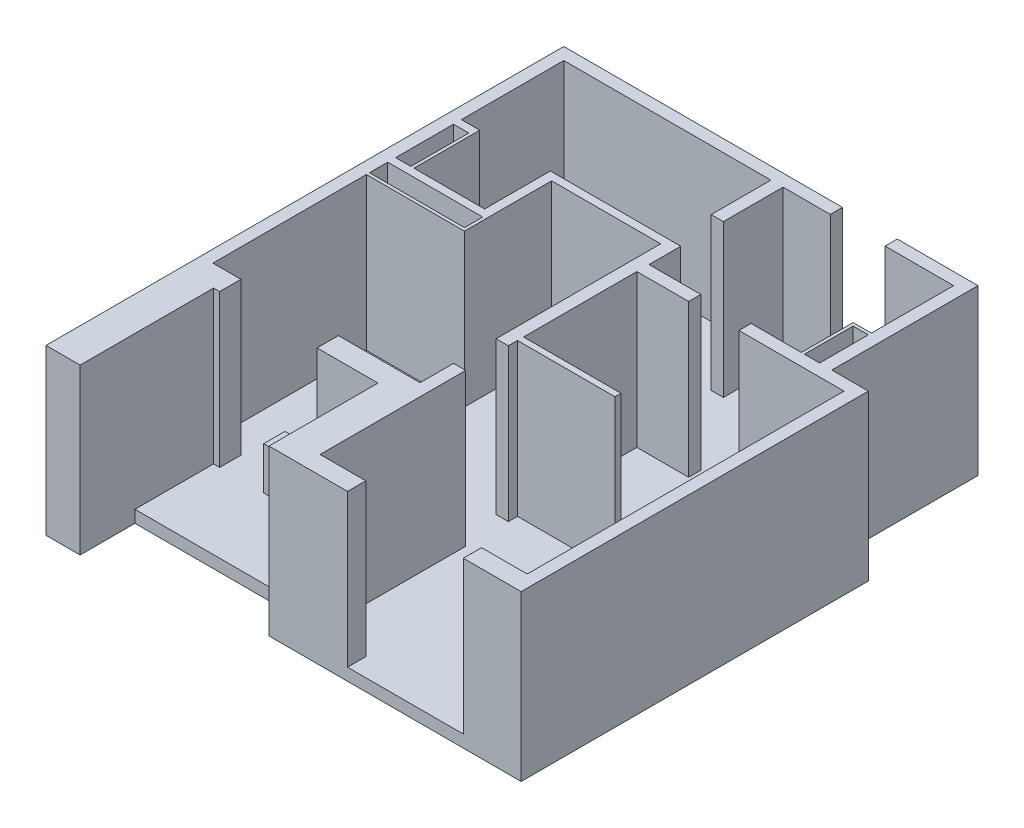
SolidWorks part; units mm, degrees
ref_plane "Спереди" through (0, 0, 0) normal (0, 0, 1) x (1, 0, 0)
ref_plane "Сверху" through (0, 0, 0) normal (0, 1, 0) x (1, 0, 0)
ref_plane "Справа" through (0, 0, 0) normal (1, 0, 0) x (0, 0, -1)
other "Configuration Table"
sketch "чертеж" plane through (0, 0, 0) normal (0, 1, 0) x (1, 0, 0)
  line L0 (-122.4645, -5934.5928) -> (200.8688, -5934.5928) construction
  line L1 (11.3792, -6202.3586) -> (334.7125, -6202.3586) construction
  line L2 (-29.7674, 42.6262) -> (294.8993, 42.6262) construction
  line L3 (-41.8231, 39.2884) -> (282.8435, 39.2884) construction
  line L4 (2418.4622, -1094.6493) -> (2743.1288, -1094.6493) construction
  line L5 (-60.4594, 42.9789) -> (264.2073, 42.9789) construction
  line L6 (-48.7728, 66.0913) -> (275.8939, 66.0913) construction
  line L7 (-42.5542, 93.9023) -> (282.1124, 93.9023) construction
  line L8 (134.2311, 87.3942) -> (458.8978, 87.3942) construction
  line L9 (-47.3906, 51.9395) -> (277.2761, 51.9395) construction
  line L10 (-66.0858, -48.647) -> (431.2475, -48.647) construction
sketch "Эскиз по чертежу" plane through (0, 0, 0) normal (0, 1, 0) x (1, 0, 0)
  line L0 (0, 0) -> (0, 8400) construction
  line L1 (0, 8400) -> (1925, 8400) construction
  line L2 (6600, 8400) -> (6600, 6000) construction
  line L4 (7200, 6000) -> (7200, 600) construction
  line L5 (7200, 600) -> (3600, 600) construction
  line L6 (3600, 600) -> (3600, 8400) construction
  line L7 (3600, 2400) -> (0, 2400) construction
  line L8 (3600, 5475) -> (0, 5475) construction
  line L32 (6600, 6000) -> (7200, 6000) construction
  line L33 (0, 900) -> (3600, 900) construction
  line L37 (0, 1050) -> (3600, 1050) construction
  line L40 (1925, 5475) -> (1925, 6550) construction
  line L42 (1925, 6550) -> (1925, 8400) construction
  line L45 (1925, 8400) -> (3600, 8400) construction
  line L46 (3600, 8400) -> (6600, 8400) construction
  line L49 (1925, 6550) -> (0, 6550) construction
  dimension "D1" = 600
  dimension "D2" = 1800
  dimension "D3" = 3600
  dimension "D4" = 1500
  dimension "D5" = 600
  dimension "D6" = 3600
  dimension "D7" = 3600
  dimension "D8" = 2400
  dimension "D9" = 2925
  dimension "D10" = 1925
  dimension "D11" = 1850
  dimension "D12" = 1350
sketch "Эскиз3" plane through (0, 0, 0) normal (0, 1, 0) x (1, 0, 0)
  line L0 (0, 0) -> (0, 8400) construction
  line L1 (7200, 6000) -> (7200, 600) construction
  line L3 (6600, 8400) -> (6600, 6000) construction
  line L11 (100, 8300) -> (3500, 8300)
  line L15 (3500, 8300) -> (3500, 7700)
  line L16 (3500, 7700) -> (3700, 7700)
  line L17 (3700, 7700) -> (3700, 8300)
  line L19 (0, 8400) -> (1925, 8400) construction
  line L20 (6500, 6100) -> (5850, 6100)
  line L21 (-100, 8500) -> (4475, 8500)
  line L22 (6500, 8300) -> (6500, 6100)
  line L24 (4475, 8500) -> (4475, 8300)
  line L25 (4475, 8300) -> (3700, 8300)
  line L26 (6700, 8500) -> (5375, 8500)
  line L29 (7100, 5900) -> (7100, 700)
  line L30 (4450, 700) -> (3700, 700)
  line L32 (6350, 500) -> (7300, 500)
  line L33 (7300, 500) -> (7300, 6100)
  line L34 (7300, 6100) -> (6700, 6100)
  line L35 (6700, 6100) -> (6700, 8500)
  line L39 (5375, 8500) -> (5375, 8300)
  line L40 (5375, 8300) -> (6500, 8300)
  line L41 (5850, 6100) -> (5850, 5900)
  line L42 (5850, 5900) -> (7100, 5900)
  line L45 (-100, 8500) -> (-100, 0)
  line L46 (-100, 0) -> (100, 0)
  line L47 (3500, 6100) -> (4550, 6100)
  line L52 (100, 0) -> (100, 8300)
  line L60 (3700, 700) -> (3700, 5900)
  line L68 (3500, 6100) -> (3500, 500)
  line L69 (4550, 6100) -> (4550, 5900)
  line L70 (4550, 5900) -> (3700, 5900)
  line L71 (7100, 700) -> (6350, 700)
  line L72 (6350, 500) -> (6350, 700)
  line L73 (3500, 500) -> (4450, 500)
  line L74 (4450, 500) -> (4450, 700)
  line L75 (7200, 600) -> (3600, 600) construction
  dimension "D1" = 3400
  dimension "D2" = 3400
  dimension "D3" = 5200
  dimension "D4" = 1300
  dimension "D5" = 200
  dimension "D6" = 2800
  dimension "D7" = 200
  dimension "D8" = 200
  dimension "D9" = 2200
  dimension "D10" = 100
  dimension "D11" = 100
  dimension "D12" = 100
  dimension "D13" = 200
  dimension "D14" = 100
  dimension "D15" = 900
  dimension "D16" = 100
  dimension "D17" = 1125
  dimension "D18" = 600
  dimension "D19" = 200
  dimension "D20" = 850
  dimension "D21" = 1900
  dimension "D22" = 750
extrude "несущие стены" add sketch "Эскиз3" along normal blind 2500 separate body
sketch "Эскиз5" plane through (0, 0, 0) normal (0, 1, 0) x (1, 0, 0)
  line L0 (100, 6620) -> (1850, 6620)
  line L2 (1850, 6620) -> (1850, 7000)
  line L3 (1850, 7000) -> (2000, 7000)
  line L4 (2000, 7000) -> (2000, 6240)
  line L5 (2000, 6240) -> (1850, 6240)
  line L6 (1850, 6240) -> (1850, 6490)
  line L7 (1850, 6490) -> (100, 6490)
  line L9 (100, 6490) -> (100, 6620)
  line L10 (100, 5410) -> (2380, 5410)
  line L12 (2380, 5410) -> (2380, 5540)
  line L17 (2380, 5540) -> (100, 5540)
  line L18 (100, 5540) -> (100, 5410)
  line L19 (3500, 5410) -> (3280, 5410)
  line L20 (3500, 6100) -> (3500, 500) construction
  line L21 (3280, 5410) -> (3280, 5540)
  line L22 (3280, 5540) -> (3500, 5540)
  line L23 (100, 0) -> (100, 8300) construction
  line L24 (3500, 5540) -> (3500, 5410)
  line L25 (1850, 8300) -> (1850, 7700)
  line L27 (1850, 7700) -> (2000, 7700)
  line L28 (2000, 7700) -> (2000, 8300)
  line L30 (2000, 8300) -> (1850, 8300)
  line L31 (100, 8300) -> (3500, 8300) construction
  line L32 (3500, 8300) -> (3500, 7700) construction
  point P34 (3280, 5475)
  dimension "D1" = 600
  dimension "D2" = 1750
  dimension "D3" = 1500
  dimension "D4" = 1680
  dimension "D5" = 130
  dimension "D6" = 700
  dimension "D7" = 700
  dimension "D8" = 950
  dimension "D9" = 900
  dimension "D10" = 220
  dimension "D11" = 150
  dimension "D12" = 130
extrude "перегородки санузла" add sketch "Эскиз5" along normal up to surface (2500 mm away) up to face at (6453.5714, 2500, -5157.1429)
sketch "Эскиз7" plane through (0, 0, 0) normal (0, 1, 0) x (1, 0, 0)
  line L0 (100, 0) -> (100, 5410) construction
  line L1 (560, 2540) -> (100, 2540)
  line L2 (460, 2190) -> (460, 0)
  line L3 (3160, 2190) -> (3160, 400)
  line L4 (3160, 400) -> (4450, 400)
  line L5 (460, 0) -> (100, 0)
  line L6 (100, 2540) -> (100, 0)
  line L7 (3280, 5410) -> (3500, 5410) construction
  line L8 (3160, 2190) -> (2160, 2190)
  line L9 (3500, 500) -> (4450, 500) construction
  line L10 (2160, 2540) -> (3500, 2540)
  line L19 (4450, 500) -> (4450, 400)
  line L20 (6350, 500) -> (7300, 500)
  line L21 (6350, 500) -> (6350, 400)
  line L22 (6350, 400) -> (7300, 400)
  line L23 (7300, 500) -> (7300, 400)
  line L24 (2160, 2190) -> (2160, 2540)
  line L25 (3500, 2540) -> (3500, 500)
  line L26 (3500, 500) -> (4450, 500)
  line L27 (3500, 5410) -> (3500, 500) construction
  line L28 (6350, 500) -> (7300, 500) construction
  line L29 (460, 2190) -> (560, 2190)
  line L30 (560, 2190) -> (560, 2540)
  line L31 (4450, 500) -> (4450, 700) construction
  line L32 (6350, 700) -> (6350, 500) construction
  dimension "D1" = 2700
  dimension "D2" = 100
  dimension "D3" = 350
  dimension "D4" = 1600
  dimension "D5" = 100
  dimension "D6" = 460
  dimension "D7" = 2870
extrude "лоджия" add sketch "Эскиз7" along normal up to surface (2500 mm away) up to face at (6453.5714, 2500, -5157.1429)
sketch "Эскиз8" plane through (0, 0, 0) normal (0, 1, 0) x (1, 0, 0)
  line L1 (50, 5460) -> (1710, 5460)
  line L2 (50, 5460) -> (50, 5060)
  line L3 (50, 5060) -> (1710, 5060)
  line L4 (1710, 5460) -> (1710, 5060)
  line L5 (100, 5410) -> (1660, 5410)
  line L6 (100, 5410) -> (100, 5110)
  line L7 (100, 5110) -> (1660, 5110)
  line L8 (1660, 5410) -> (1660, 5110)
  line L9 (100, 5410) -> (2380, 5410) construction
  line L10 (100, 2540) -> (100, 5410) construction
  dimension "D1" = 350
  dimension "D2" = 50
  dimension "D3" = 50
  dimension "D4" = 50
  dimension "D5" = 1610
  dimension "D6" = 50
extrude "вытяжка кухня" add sketch "Эскиз8" along normal up to surface (2500 mm away) up to face at (6453.5714, 2500, -5142.8571)
sketch "Эскиз9" plane through (0, 0, 0) normal (0, 1, 0) x (1, 0, 0)
  line L1 (6550, 6950) -> (6200, 6950)
  line L2 (6550, 6950) -> (6550, 6050)
  line L3 (6550, 6050) -> (6200, 6050)
  line L4 (6200, 6950) -> (6200, 6050)
  line L6 (6500, 6100) -> (5850, 6100) construction
  line L7 (6250, 6900) -> (6500, 6900)
  line L8 (6250, 6900) -> (6250, 6100)
  line L9 (6250, 6100) -> (6500, 6100)
  line L10 (6500, 6900) -> (6500, 6100)
  line L11 (6500, 8300) -> (6500, 6100) construction
  line L12 (50, 6540) -> (400, 6540)
  line L14 (400, 6540) -> (400, 5490)
  line L16 (400, 5490) -> (50, 5490)
  line L17 (50, 5490) -> (50, 6540)
  line L18 (100, 6490) -> (350, 6490)
  line L19 (350, 6490) -> (350, 5540)
  line L20 (350, 5540) -> (100, 5540)
  line L21 (100, 5540) -> (100, 6490)
  line L22 (1850, 6490) -> (1850, 6240) construction
  line L23 (100, 6490) -> (1850, 6490) construction
  point P13 (6375, 6950)
  dimension "D1" = 850
  dimension "D2" = 50
  dimension "D3" = 50
  dimension "D4" = 300
  dimension "D5" = 50
  dimension "D6" = 50
  dimension "D7" = 50
  dimension "D8" = 50
  dimension "D9" = 50
  dimension "D10" = 50
  dimension "D11" = 1450
extrude "зсс" add sketch "Эскиз9" along normal up to surface (2500 mm away) up to face at (6453.5714, 2500, -5142.8571)
sketch "Эскиз11" plane through (0, 0, 0) normal (0, 1, 0) x (1, 0, 0)
  line L1 (2160, 2540) -> (1284, 2540)
  line L2 (2160, 2540) -> (2160, 2190)
  line L3 (2160, 2190) -> (1284, 2190)
  line L4 (1284, 2540) -> (1284, 2190)
  line L5 (560, 2190) -> (560, 2540) construction
  dimension "D1" = 724
extrude "лоджияперегородка" add sketch "Эскиз11" along normal blind 700
sketch "Эскиз4" plane through (0, 0, 0) normal (0, 1, 0) x (1, 0, 0)
  line L8 (-100, 8500) -> (6700, 8500)
  line L9 (6700, 8500) -> (6700, 6100)
  line L10 (6700, 6100) -> (7300, 6100)
  line L11 (7300, 6100) -> (7300, 400)
  line L13 (3160, 400) -> (3160, 900)
  line L14 (3160, 900) -> (460, 900)
  line L17 (-100, 0) -> (-100, 8500)
  line L18 (6700, 6100) -> (6700, 8500) construction
  line L19 (6700, 8500) -> (5375, 8500) construction
  line L23 (0, 900) -> (3600, 900) construction
  line L24 (460, 900) -> (460, 0)
  line L25 (460, 0) -> (-100, 0)
  line L26 (3160, 400) -> (7300, 400)
  line L27 (3160, 2190) -> (3160, 400) construction
  line L28 (460, 0) -> (460, 2190) construction
  line L29 (-100, 0) -> (460, 0) construction
extrude "пол" add sketch "Эскиз4" against normal blind 200
sketch "Эскиз что надо" [suppressed] plane through (0, 0, 0) normal (0, 1, 0) x (1, 0, 0)
  line L0 (5525, 8300) -> (5525, 6100) construction
  line L5 (2000, 6240) -> (2000, 7000) construction
  line L6 (1850, 7000) -> (2000, 7000)
  line L7 (1850, 7000) -> (1850, 6620)
  line L8 (1850, 6620) -> (2000, 6620)
  line L9 (2000, 7000) -> (2000, 6620)
  line L10 (1850, 6490) -> (1850, 6240) construction
  line L11 (1850, 7700) -> (2000, 7700)
  line L12 (1850, 7700) -> (1850, 7320)
  line L13 (1850, 7320) -> (2000, 7320)
  line L14 (2000, 7700) -> (2000, 7320)
  line L15 (1850, 5540) -> (2000, 5540)
  line L16 (1850, 5540) -> (1850, 5790)
  line L17 (1850, 5790) -> (2000, 5790)
  line L18 (2000, 5540) -> (2000, 5790)
  line L19 (1850, 6490) -> (2000, 6490)
  line L20 (1850, 6490) -> (1850, 6240)
  line L21 (1850, 6240) -> (2000, 6240)
  line L22 (2000, 6490) -> (2000, 6240)
  line L23 (1850, 7000) -> (1850, 6620) construction
  line L28 (3500, 7700) -> (3700, 7700) construction
  line L29 (3500, 7700) -> (3500, 7420) construction
  line L30 (3500, 7420) -> (3700, 7420) construction
  line L31 (3700, 7700) -> (3700, 7420) construction
  line L32 (4550, 5900) -> (4550, 6100) construction
  line L35 (5850, 5900) -> (5450, 5900)
  line L36 (5850, 5900) -> (5850, 6100)
  line L37 (5850, 6100) -> (5450, 6100)
  line L38 (5450, 5900) -> (5450, 6100)
  line L39 (5375, 8300) -> (6500, 8300) construction
  line L40 (2000, 7420) -> (3500, 7420) construction
  line L41 (5375, 8500) -> (5375, 8300) construction
  line L42 (2380, 5540) -> (400, 5540) construction
  line L43 (1284, 2540) -> (2160, 2540)
  line L44 (1284, 2540) -> (1284, 2190)
  line L46 (1284, 2190) -> (2160, 2190)
  line L47 (2000, 7320) -> (2000, 6620) construction
  line L48 (2160, 2540) -> (2160, 2190)
  point P32 (1925, 6490)
  dimension "D8" = 900
  dimension "D1" = 700
  dimension "D2" = 700
  dimension "D3" = 150
  dimension "D5" = 100
sketch "Эскиз13" [suppressed] plane through (0, 0, 0) normal (0, 1, 0) x (1, 0, 0)
  line L1 (1850, 6490) -> (2000, 6490)
  line L2 (1850, 6490) -> (1850, 6240)
  line L3 (1850, 6240) -> (2000, 6240)
  line L4 (2000, 6490) -> (2000, 6240)
  line L5 (1850, 7000) -> (2000, 7000)
  line L6 (1850, 7000) -> (1850, 6620)
  line L7 (1850, 6620) -> (2000, 6620)
  line L8 (2000, 7000) -> (2000, 6620)
  line L9 (1284, 2540) -> (2160, 2540) construction
  line L10 (1284, 2540) -> (1284, 2190) construction
  line L11 (1284, 2190) -> (2160, 2190) construction
  line L12 (2160, 2540) -> (2160, 2190) construction
extrude "санузел вырез" [suppressed] cut sketch "Эскиз13" along normal through all
sketch "Эскиз14" [suppressed] plane through (0, 0, 0) normal (0, 1, 0) x (1, 0, 0)
  line L1 (5850, 6100) -> (5450, 6100)
  line L2 (5850, 6100) -> (5850, 5900)
  line L3 (5850, 5900) -> (5450, 5900)
  line L4 (5450, 6100) -> (5450, 5900)
  line L5 (1850, 5540) -> (2000, 5540)
  line L6 (1850, 5540) -> (1850, 5790)
  line L7 (1850, 5790) -> (2000, 5790)
  line L8 (2000, 5540) -> (2000, 5790)
  line L9 (1850, 7700) -> (2000, 7700)
  line L10 (1850, 7700) -> (1850, 7320)
  line L11 (1850, 7320) -> (2000, 7320)
  line L12 (2000, 7700) -> (2000, 7320)
extrude "наращивание стен" [suppressed] add sketch "Эскиз14" along normal through all separate body
sketch "Эскиз15" [suppressed] plane through (0, 0, 0) normal (0, 1, 0) x (1, 0, 0)
  line L12 (3700, 7700) -> (3500, 7700) construction
  line L29 (3700, 7420) -> (3700, 7700)
  line L30 (3700, 7700) -> (3500, 7700)
  line L32 (3500, 7700) -> (3500, 7420)
  line L36 (3500, 7420) -> (3700, 7420)
  line L39 (3500, 7700) -> (3500, 7420) construction
  line L40 (3700, 7700) -> (3700, 7420) construction
  line L46 (3500, 7700) -> (3700, 7700) construction
  line L47 (2000, 7420) -> (2800, 7420) construction
  line L48 (2000, 7420) -> (2000, 7500) construction
  line L49 (2000, 7500) -> (2800, 7500) construction
  line L50 (2800, 7420) -> (2800, 7500) construction
  dimension "D1" = 80
  dimension "D2" = 700
extrude "наращивание стен 2" [suppressed] add sketch "Эскиз15" along normal through all separate body
sketch "Эскиз37" [suppressed] plane through (0, 0, 0) normal (0, 1, 0) x (1, 0, 0)
  line L0 (3700, 700) -> (7100, 700)
  line L1 (7100, 700) -> (7100, 5900)
  line L2 (7100, 5900) -> (5850, 5900)
  line L3 (5850, 5900) -> (5850, 6100)
  line L7 (5850, 6100) -> (4550, 6100)
  line L8 (4550, 6100) -> (4550, 5900)
  line L9 (4550, 5900) -> (3700, 5900)
  line L10 (3700, 5900) -> (3700, 700)
extrude "зал" [suppressed] add sketch "Эскиз37" along normal blind 50 separate body
sketch "Эскиз38" [suppressed] plane through (0, 0, 0) normal (0, 1, 0) x (1, 0, 0)
  line L0 (460, 950) -> (3160, 950)
  line L1 (3160, 950) -> (3160, 2190)
  line L2 (3160, 2190) -> (2160, 2190)
  line L3 (2160, 2190) -> (2160, 2540)
  line L4 (2160, 2540) -> (3500, 2540)
  line L5 (3500, 5410) -> (3500, 2540) construction
  line L6 (3500, 2540) -> (3500, 5410)
  line L7 (3500, 5410) -> (3280, 5410)
  line L8 (3280, 5410) -> (3280, 5540)
  line L9 (3280, 5540) -> (2380, 5540)
  line L10 (2380, 5540) -> (2380, 5410)
  line L11 (2380, 5410) -> (1710, 5410)
  line L12 (1710, 5410) -> (1710, 5060)
  line L13 (1710, 5060) -> (100, 5060)
  line L14 (100, 5060) -> (100, 2540)
  line L15 (100, 2540) -> (560, 2540)
  line L16 (560, 2540) -> (560, 2190)
  line L17 (560, 2190) -> (460, 2190)
  line L18 (460, 2190) -> (460, 950)
  line L19 (460, 0) -> (460, 2190) construction
  line L20 (460, 900) -> (3160, 900) construction
  line L21 (3500, 2540) -> (2160, 2540) construction
  line L22 (3500, 2540) -> (1284, 2540) construction
  dimension "D1" = 50
extrude "кухня лоджия" [suppressed] add sketch "Эскиз38" along normal blind 50 separate body
sketch "Эскиз40" [suppressed] plane through (0, 0, 0) normal (0, 1, 0) x (1, 0, 0)
  line L0 (6200, 6100) -> (6200, 6950)
  line L1 (6200, 6950) -> (6500, 6950)
  line L2 (6500, 6950) -> (6500, 8300)
  line L3 (6500, 8300) -> (3700, 8300)
  line L4 (3700, 8300) -> (3700, 7420)
  line L5 (3700, 7420) -> (3500, 7420)
  line L6 (3500, 7420) -> (3500, 8300)
  line L7 (3500, 8300) -> (2000, 8300)
  line L8 (2000, 8300) -> (2000, 5540)
  line L9 (2000, 5540) -> (3500, 5540)
  line L10 (3500, 5540) -> (3500, 6100)
  line L11 (3500, 6100) -> (6200, 6100)
extrude "прихожия" [suppressed] add sketch "Эскиз40" along normal blind 50 separate body
sketch "Эскиз42" [suppressed] plane through (0, 0, 0) normal (0, 1, 0) x (1, 0, 0)
  line L0 (100, 8300) -> (100, 6620)
  line L1 (100, 6620) -> (2000, 6620)
  line L4 (2000, 6620) -> (2000, 7320)
  line L5 (2000, 7320) -> (1850, 7320)
  line L6 (1850, 7320) -> (1850, 8300)
  line L7 (1850, 8300) -> (100, 8300)
  line L8 (2000, 8300) -> (2000, 5540) construction
  line L9 (2000, 6620) -> (100, 6620) construction
  line L10 (2000, 8300) -> (2000, 5540) construction
extrude "ванная" [suppressed] add sketch "Эскиз42" along normal blind 50 separate body
sketch "Эскиз45" [suppressed] plane through (0, 50, 0) normal (0, 1, 0) x (1, 0, 0)
  line L0 (400, 6490) -> (2000, 6490) construction
  line L1 (850, 6490) -> (930, 6490)
  line L2 (850, 6490) -> (850, 5540)
  line L3 (850, 5540) -> (930, 5540)
  line L4 (930, 6490) -> (930, 5540)
  line L5 (2380, 5540) -> (400, 5540) construction
  line L7 (1850, 5790) -> (1850, 5540) construction
  dimension "D1" = 80
  dimension "D2" = 920
extrude "Бобышка-Вытянуть33" [suppressed] add sketch "Эскиз45" along normal blind 1200 separate body
sketch "Эскиз46" [suppressed] plane through (930, 0, 0) normal (1, 0, 0) x (0, 0, -1)
  line L0 (5540, 50) -> (6490, 50) construction
  line L1 (5835, 440) -> (6195, 440)
  line L2 (5835, 440) -> (5835, 80)
  line L3 (5835, 80) -> (6195, 80)
  line L4 (6195, 440) -> (6195, 80)
  line L6 (6015, 50) -> (6015, 440) construction
  line L7 (6490, 1250) -> (6490, 50) construction
  line L8 (6015, 440) -> (6015, 950) construction
  line L9 (5940, 1040) -> (6090, 1040)
  line L10 (5940, 1040) -> (5940, 950)
  line L11 (5940, 950) -> (6090, 950)
  line L12 (6090, 1040) -> (6090, 950)
  line L14 (6280, 550) -> (6480, 550)
  line L15 (6280, 550) -> (6280, 50)
  line L16 (6280, 50) -> (6480, 50)
  line L17 (6480, 550) -> (6480, 50)
  point P4 (6015, 50)
  dimension "D1" = 360
  dimension "D2" = 390
  dimension "D3" = 150
  dimension "D4" = 90
  dimension "D5" = 900
  dimension "D6" = 30
  dimension "D7" = 200
  dimension "D8" = 500
  dimension "D9" = 10
extrude "Вырез-Вытянуть2" [suppressed] cut sketch "Эскиз46" against normal up to surface (80 mm away)
sketch "Эскиз43" [suppressed] plane through (0, 0, 0) normal (0, 1, 0) x (1, 0, 0)
  line L0 (930, 6490) -> (930, 5540)
  line L1 (930, 5540) -> (1850, 5540)
  line L2 (2380, 5540) -> (400, 5540) construction
  line L3 (1850, 5540) -> (1850, 5790)
  line L4 (1850, 5790) -> (2000, 5790)
  line L5 (2000, 5790) -> (2000, 6490)
  line L8 (2000, 6490) -> (930, 6490)
extrude "толчок" [suppressed] add sketch "Эскиз43" along normal blind 50 separate body
sketch "Эскиз47" plane through (0, 0, 0) normal (0, 1, 0) x (1, 0, 0)
  line L0 (3500, 5410) -> (3500, 2540) construction
  line L1 (1710, 6490) -> (3500, 6490) construction
  line L2 (1710, 6490) -> (1710, 4290) construction
  line L3 (1710, 4290) -> (3500, 4290) construction
  line L4 (3500, 6490) -> (3500, 4290) construction
  line L5 (1560, 5410) -> (1560, 6620) construction
  line L6 (400, 6490) -> (1850, 6490) construction
  line L7 (1710, 5060) -> (1710, 5410) construction
  line L8 (100, 5410) -> (1660, 5410) construction
  line L9 (2000, 6240) -> (2000, 7000) construction
  line L10 (1850, 6620) -> (100, 6620) construction
  line L11 (1850, 8300) -> (2000, 8300)
  line L12 (1850, 8300) -> (1850, 6620)
  line L13 (1560, 6620) -> (1710, 6620) construction
  line L14 (1710, 6620) -> (1710, 6490) construction
  line L15 (1850, 6620) -> (2000, 6620)
  line L16 (2000, 8300) -> (2000, 6620)
  line L17 (3500, 5410) -> (3500, 2540) construction
  line L18 (3500, 3790) -> (3700, 3790)
  line L19 (3500, 3790) -> (3500, 3090)
  line L20 (3500, 3090) -> (3700, 3090)
  line L21 (3700, 3790) -> (3700, 3090)
  line L22 (3700, 700) -> (3700, 5900) construction
  line L24 (3500, 2540) -> (2160, 2540) construction
  line L25 (2000, 6240) -> (2000, 7000) construction
  line L26 (400, 6490) -> (1560, 6490)
  line L27 (400, 6490) -> (400, 6620)
  line L28 (400, 6620) -> (1560, 6620)
  line L29 (1560, 6490) -> (1560, 6620)
  line L30 (3500, 5540) -> (1710, 5540)
  line L31 (3500, 5540) -> (3500, 5410)
  line L32 (3500, 5410) -> (1710, 5410)
  line L33 (1710, 5540) -> (1710, 5410)
  line L34 (1850, 6490) -> (2000, 6490)
  line L35 (1850, 6490) -> (1850, 6240)
  line L36 (1850, 6240) -> (2000, 6240)
  line L37 (2000, 6490) -> (2000, 6240)
  dimension "D1" = 700
  dimension "D3" = 550
extrude "Вырез-Вытянуть3" cut sketch "Эскиз47" along normal through all
sketch "Эскиз48" plane through (0, 0, 0) normal (0, 1, 0) x (1, 0, 0)
  line L0 (5850, 5900) -> (7100, 5900) construction
  line L1 (1560, 6490) -> (1710, 6490)
  line L2 (1560, 6490) -> (1560, 5540)
  line L3 (1560, 5540) -> (1710, 5540)
  line L4 (1710, 6490) -> (1710, 5540)
  line L5 (5850, 6100) -> (5375, 6100)
  line L6 (5850, 6100) -> (5850, 5900)
  line L7 (5850, 5900) -> (5375, 5900)
  line L8 (5375, 6100) -> (5375, 5900)
  line L11 (3700, 6620) -> (3700, 6100)
  line L12 (2000, 6490) -> (3500, 6490)
  line L13 (3500, 6490) -> (3500, 6100)
  line L14 (3500, 6100) -> (3700, 6100)
  line L15 (3500, 6100) -> (3500, 3790) construction
  line L16 (4550, 6100) -> (3500, 6100) construction
  line L17 (3700, 3790) -> (3700, 5900) construction
  line L18 (2000, 6490) -> (2000, 6620)
  line L19 (3700, 7700) -> (3500, 7700)
  line L20 (3500, 7700) -> (3500, 7320)
  line L21 (3500, 7320) -> (3700, 7320)
  line L22 (3700, 7320) -> (3700, 7700)
  line L23 (3700, 6620) -> (2000, 6620)
  line L24 (3700, 3790) -> (3500, 3790) construction
  line L25 (3700, 4040) -> (5300, 4040)
  line L26 (3700, 4040) -> (3700, 3940)
  line L27 (3700, 3940) -> (5300, 3940)
  line L28 (5300, 4040) -> (5300, 3940)
  line L29 (7100, 5900) -> (7100, 700) construction
  line L30 (5375, 8300) -> (5375, 6100) construction
  line L31 (4550, 5900) -> (4550, 6100) construction
  dimension "D1" = 825
  dimension "D2" = 700
  dimension "D3" = 100
  dimension "D4" = 150
  dimension "D5" = 1800
extrude "Бобышка-Вытянуть34" add sketch "Эскиз48" along normal through all
